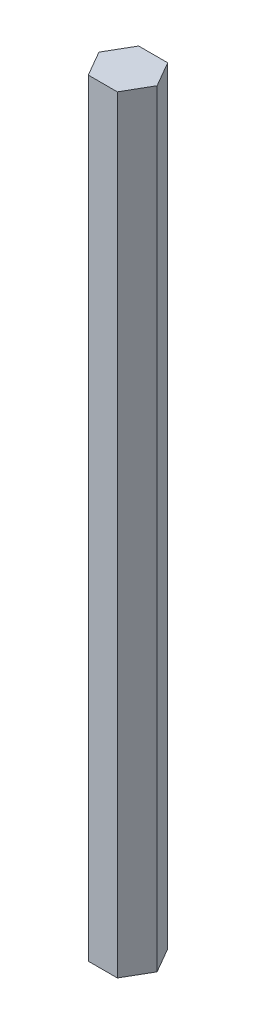
SolidWorks part; units mm, degrees
material "6061-T6 (SS)"
ref_plane "Front" through (0, 0, 0) normal (0, 0, 1) x (1, 0, 0)
ref_plane "Top" through (0, 0, 0) normal (0, 1, 0) x (1, 0, 0)
ref_plane "Right" through (0, 0, 0) normal (1, 0, 0) x (0, 0, -1)
sketch "Sketch1" plane through (0, 0, 0) normal (0, 1, 0) x (1, 0, 0)
  line L1 (2.8868, 0) -> (1.4434, 2.5)
  line L2 (1.4434, 2.5) -> (-1.4434, 2.5)
  line L3 (-1.4434, 2.5) -> (-2.8868, 0)
  line L4 (-2.8868, 0) -> (-1.4434, -2.5)
  line L5 (-1.4434, -2.5) -> (1.4434, -2.5)
  line L6 (1.4434, -2.5) -> (2.8868, 0)
  circle A0 centre (0, 0) radius 2.5 construction
  dimension "D1" = 5
extrude "Boss-Extrude1" add sketch "Sketch1" along normal mid plane 76.2
ref_axis "Axis1" through (0, 49.5981, 0) along (0, -1, 0)
